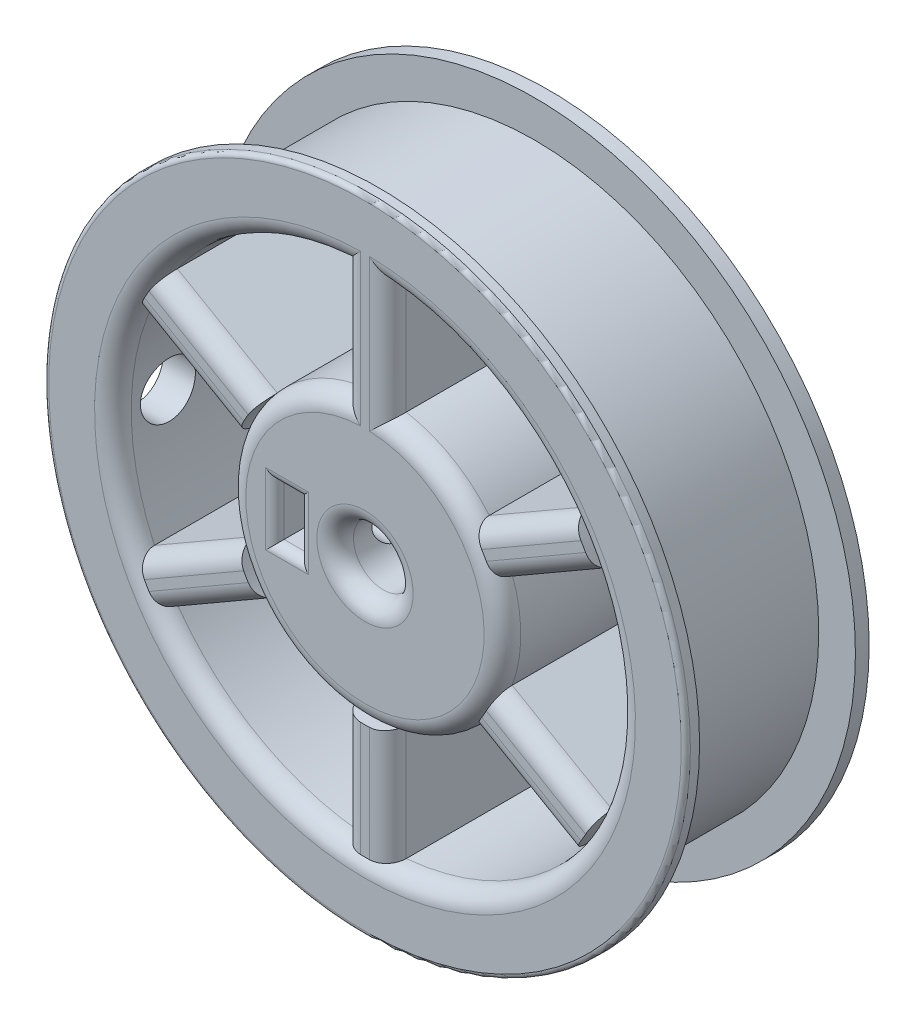
SolidWorks part; units mm, degrees
ref_plane "Front" through (0, 0, 0) normal (0, 0, 1) x (1, 0, 0)
ref_plane "Top" through (0, 0, 0) normal (0, 1, 0) x (1, 0, 0)
ref_plane "Right" through (0, 0, 0) normal (1, 0, 0) x (0, 0, -1)
sketch "Sketch1" plane through (0, 0, 0) normal (0, 0, 1) x (1, 0, 0)
  circle A0 centre (0, 0) radius 15
  circle A3 centre (0, 0) radius 3.25
  dimension "D1" = 30
  dimension "D2" = 6.5
extrude "Boss-Extrude1" add sketch "Sketch1" along normal blind 20
sketch "Sketch2" plane through (0, 0, 0) normal (0, 0, 1) x (1, 0, 0)
  circle A0 centre (0, 0) radius 35
  circle A1 centre (0, 0) radius 27.5
  dimension "D1" = 70
  dimension "D2" = 7.5
extrude "Boss-Extrude2" add sketch "Sketch2" along normal blind 20
sketch "Sketch4" plane through (0, 0, 0) normal (0, 0, 1) x (1, 0, 0)
  line L0 (0, 27.5) -> (0, 15) construction
  line L1 (0, -50) -> (0, 50) construction
  line L2 (-2.5, 27.3861) -> (-2.5, 14.7902)
  line L3 (2.5, 14.7902) -> (2.5, 27.3861)
  circle A0 centre (0, 0) radius 27.5 construction
  circle A1 centre (0, 0) radius 15 construction
  arc A2 (-2.5, 14.7902) -> (2.5, 14.7902) centre (0, 0) cw
  arc A3 (-2.5, 27.3861) -> (2.5, 27.3861) centre (0, 0) cw
  dimension "D1" = 5
extrude "Boss-Extrude3" add sketch "Sketch4" along normal up to surface (20 mm away) up to face at (35, 0, 20)
fillet "Fillet2" radius 2 2 edges at (2.5, 21.0882, 20) (-2.5, 21.0882, 20)
fillet "Fillet3" radius 0.5 1 edges at (35, 0, 20)
fillet "Fillet4" radius 2 3 edges at (3.25, 0, 20) (0, -27.5, 20) (0, -15, 20)
sketch "Sketch5" plane through (0, 0, 0) normal (1, 0, 0) x (0, 0, -1)
  line L0 (0, 0) -> (-32.2104, 0) construction
pattern_circular "CirPattern1" count 6 over 360 about axis through (0, 0, 0) along (0, 0, 1) of "Boss-Extrude3", "Fillet2" reverse direction yes
sketch "Sketch6" plane through (0, 0, 0) normal (1, 0, 0) x (0, 0, -1)
  line L0 (0, 35) -> (-19.5, 35) construction
  line L1 (-1.5, 35) -> (-18.5, 35)
  line L2 (-1.5, 35) -> (-1.5, 31)
  line L3 (-1.5, 31) -> (-18.5, 31)
  line L4 (-18.5, 35) -> (-18.5, 31)
  line L5 (0, -35) -> (0, 35) construction
  line L6 (-20, 35) -> (-20, -35) construction
  dimension "D1" = 1.5
  dimension "D2" = 1.5
  dimension "D3" = 4
revolve "Cut-Revolve1" cut sketch "Sketch6" angle 360 about L0
sketch "Sketch7" plane through (0, 0, 0) normal (0, 0, 1) x (1, 0, 0)
  line L0 (50, 0) -> (-50, 0) construction
  line L1 (-9.825, -2.9) -> (-7.175, -2.9)
  line L2 (-9.825, -2.9) -> (-9.825, 2.9)
  line L3 (-9.825, 2.9) -> (-7.175, 2.9)
  line L4 (-7.175, -2.9) -> (-7.175, 2.9)
  line L5 (-9.825, -2.9) -> (-7.175, 2.9) construction
  line L6 (-9.825, 2.9) -> (-7.175, -2.9) construction
  point P0 (-8.5, 0)
  dimension "D1" = 5.8
  dimension "D2" = 2.65
  dimension "D3" = 8.5
extrude "Cut-Extrude1" cut sketch "Sketch7" along normal up to surface (20 mm away) up to face at (5.25, 0, 20)
sketch "Sketch8" plane through (0, 0, 0) normal (1, 0, 0) x (0, 0, -1)
  line L0 (0, 0) -> (-32.2104, 0) construction
  line L1 (0, 50) -> (0, -50) construction
  circle A0 centre (-6, 0) radius 2
  circle A1 centre (-14, 0) radius 2
  dimension "D1" = 4
  dimension "D2" = 8
  dimension "D3" = 6
extrude "Cut-Extrude2" cut sketch "Sketch8" against normal up to surface (15 mm away) up to face at (-14.5293, 0, 9)
ref_plane "Plane1" through (-20, 0, 0) normal (1, 0, 0) x (0, 0, -1)
sketch "Sketch9" plane through (-20, 0, 0) normal (1, 0, 0) x (0, 0, -1)
  line L0 (0, 0) -> (-32.2104, 0) construction
  line L1 (0, -11.528) -> (0, 11.528) construction
  circle A0 centre (-6, 0) radius 3
  circle A1 centre (-14, 0) radius 3
  dimension "D1" = 6
  dimension "D2" = 6
  dimension "D3" = 8
extrude "Cut-Extrude3" cut sketch "Sketch9" against normal up to surface (11 mm away) up to face at (-31, 0, 1.5)
fillet "Fillet5" radius 1 4 edges at (-8.5, -2.9, 20) (-9.825, 0, 20) (-8.5, 2.9, 20) (-7.175, 0, 20)
